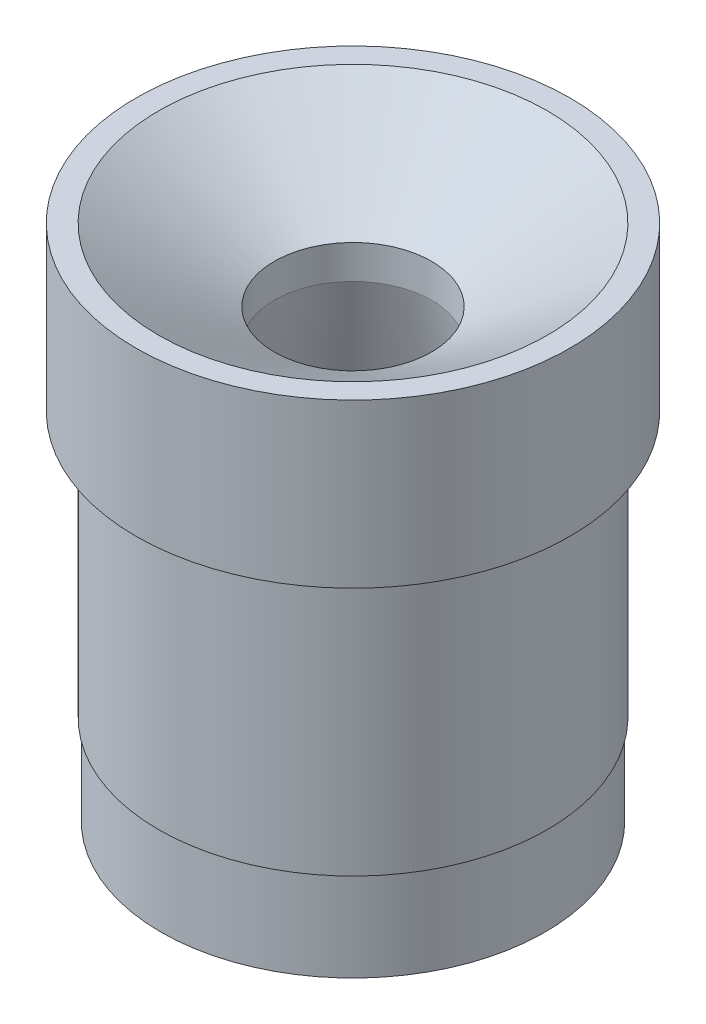
SolidWorks part; units mm, degrees
material "LE Phenolic"
ref_plane "Front Plane" through (0, 0, 0) normal (0, 0, 1) x (1, 0, 0)
ref_plane "Top Plane" through (0, 0, 0) normal (0, 1, 0) x (1, 0, 0)
ref_plane "Right Plane" through (0, 0, 0) normal (1, 0, 0) x (0, 0, -1)
sketch "Sketch1" plane through (0, 0, 0) normal (0, 1, 0) x (1, 0, 0)
  circle A0 centre (0, 0) radius 24.511
  dimension "D1" = 49.022
extrude "Boss-Extrude1" [suppressed] add sketch "Sketch1" along normal blind 18.415
sketch "Sketch2" [suppressed] plane through (0, 0, 0) normal (0, -1, 0) x (1, 0, 0)
  circle A0 centre (0, 0) radius 21.463
  dimension "D1" = 42.926
extrude "Boss-Extrude2" [suppressed] add sketch "Sketch2" along normal blind 44.45
ref_axis "Axis1" [suppressed] through (0, -44.45, 0) along (0, 1, 0)
sketch "Sketch4" plane through (0, 0, 0) normal (1, 0, 0) x (0, 0, -1)
  line L0 (24.511, 0) -> (24.511, 18.415)
  line L1 (24.511, 0) -> (21.971, 0)
  line L3 (21.717, -40.132) -> (20.066, -40.132)
  line L4 (20.066, -40.132) -> (8.89, 6.4194)
  line L5 (8.89, 6.4194) -> (8.89, 10.2294)
  line L6 (8.89, 10.2294) -> (21.971, 18.415)
  line L7 (21.971, 18.415) -> (24.511, 18.415)
  line L8 (21.717, -40.132) -> (21.717, -29.972)
  line L9 (21.717, -29.972) -> (21.971, -29.972)
  line L10 (21.971, -29.972) -> (21.971, 0)
  dimension "D1" = 18.415
  dimension "D2" = 21.717
  dimension "D3" = 3.81
  dimension "D4" = 8.89
  dimension "D5" = 21.971
  dimension "D6" = 24.511
  dimension "D7" = 13.5
  dimension "D8" = 20.066
  dimension "D9" = 10.16
  dimension "D10" = 40.132
ref_axis "Axis2" through (0, 21.5582, 0) along (0, -1, 0)
revolve "Revolve1" add sketch "Sketch4" angle 360 about axis through (0, 21.5582, 0) along (0, -1, 0)
